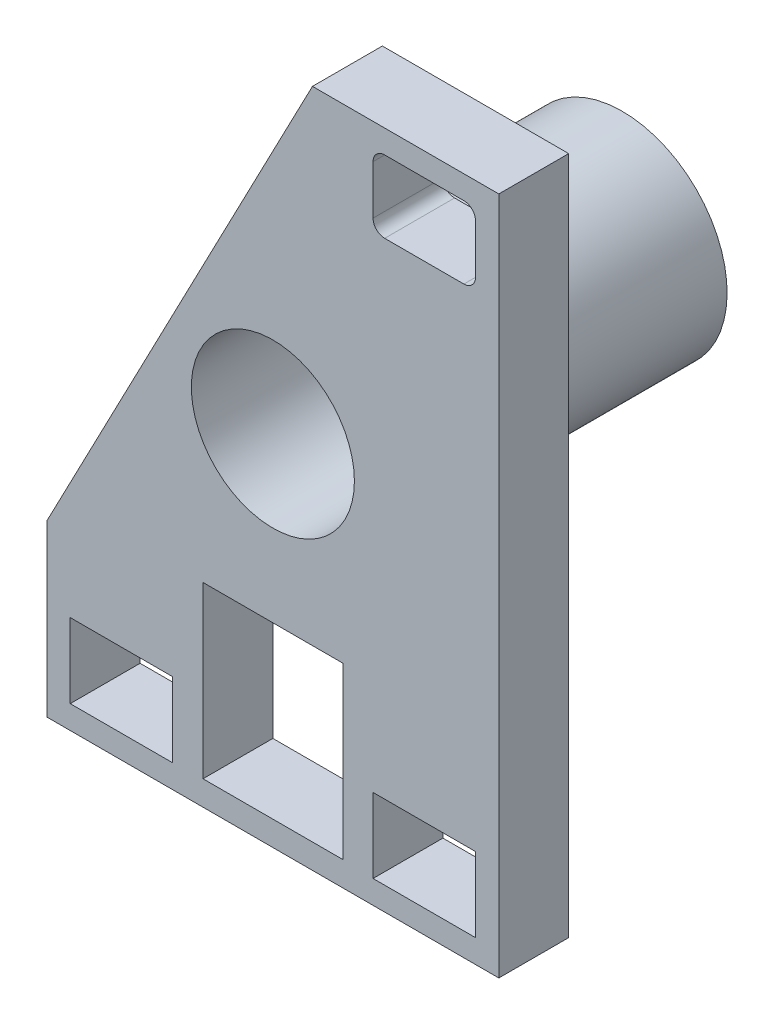
SolidWorks part; units mm, degrees
ref_plane "Front Plane" through (0, 0, 0) normal (0, 0, 1) x (1, 0, 0)
ref_plane "Top Plane" through (0, 0, 0) normal (0, 1, 0) x (1, 0, 0)
ref_plane "Right Plane" through (0, 0, 0) normal (1, 0, 0) x (0, 0, -1)
sketch "Sketch2" plane through (0, 0, 0) normal (0, 0, 1) x (1, 0, 0)
  line L0 (5.1046, -104.9632) -> (70.1046, -104.9632) construction
  line L1 (5.1046, 135.0368) -> (5.1046, -104.9632) construction
  line L2 (70.1046, -104.9632) -> (70.1046, 135.0368) construction
  line L3 (70.1046, 135.0368) -> (26.1046, 135.0368) construction
  line L4 (26.1046, 135.0368) -> (-59.8954, -32.9944) construction
  line L5 (-59.8954, -32.9944) -> (-59.8954, -104.9632) construction
  line L6 (-59.8954, -104.9632) -> (5.1046, -104.9632) construction
  line L7 (92.1046, 148.2211) -> (92.1046, -130.9632) construction
  line L8 (48.1046, 154.3078) -> (48.1046, -150.1586) construction
  line L9 (48.1046, 135.0368) -> (92.1046, 135.0368) construction
  line L10 (22.1046, 160.5368) -> (102.1046, 160.5368)
  line L11 (48.1046, 150.5368) -> (92.1046, 150.5368)
  line L12 (48.1046, 150.5368) -> (48.1046, 119.5368)
  line L13 (48.1046, 119.5368) -> (92.1046, 119.5368)
  line L14 (92.1046, 150.5368) -> (92.1046, 119.5368)
  line L15 (48.1046, 150.5368) -> (92.1046, 119.5368) construction
  line L16 (48.1046, 119.5368) -> (92.1046, 150.5368) construction
  line L17 (48.1046, -88.9632) -> (92.1046, -88.9632)
  line L18 (48.1046, -88.9632) -> (48.1046, -120.9632)
  line L19 (48.1046, -120.9632) -> (92.1046, -120.9632)
  line L20 (92.1046, -88.9632) -> (92.1046, -120.9632)
  line L21 (48.1046, -88.9632) -> (92.1046, -120.9632) construction
  line L22 (48.1046, -120.9632) -> (92.1046, -88.9632) construction
  line L23 (-81.8954, -88.9632) -> (-37.8954, -88.9632)
  line L24 (-81.8954, -88.9632) -> (-81.8954, -120.9632)
  line L25 (-81.8954, -120.9632) -> (-37.8954, -120.9632)
  line L26 (-37.8954, -88.9632) -> (-37.8954, -120.9632)
  line L27 (-81.8954, -88.9632) -> (-37.8954, -120.9632) construction
  line L28 (-81.8954, -120.9632) -> (-37.8954, -88.9632) construction
  line L29 (102.1046, 160.5368) -> (102.1046, -130.9632)
  line L30 (102.1046, -130.9632) -> (-91.8954, -130.9632)
  line L31 (-91.8954, -130.9632) -> (-91.8954, -57.9632)
  line L32 (22.1046, 160.5368) -> (-91.8954, -57.9632)
  line L34 (-24.8954, -47.396) -> (35.1046, -47.396)
  line L35 (-24.8954, -47.396) -> (-24.8954, -120.396)
  line L36 (-24.8954, -120.396) -> (35.1046, -120.396)
  line L37 (35.1046, -47.396) -> (35.1046, -120.396)
  line L38 (-24.8954, -47.396) -> (35.1046, -120.396) construction
  line L39 (-24.8954, -120.396) -> (35.1046, -47.396) construction
  circle A0 centre (5.1046, 15.0368) radius 45 construction
  point P13 (70.1046, 135.0368)
  point P30 (5.1046, -83.896)
  dimension "D7" = 90
  dimension "D8" = 10
  dimension "D1" = 240
  dimension "D2" = 130
  dimension "D3" = 44
  dimension "D4" = 31
  dimension "D5" = 32
  dimension "D6" = 44
  dimension "D9" = 10
  dimension "D10" = 10
  dimension "D11" = 10
  dimension "D12" = 73
  dimension "D13" = 60
  dimension "D14" = 80
  dimension "D15" = 73
extrude "Boss-Extrude1" add sketch "Sketch2" along normal blind 30
sketch "Sketch3" plane through (0, 0, 0) normal (0, 0, -1) x (-1, 0, 0)
  line L0 (-92.1046, 150.5368) -> (-48.1046, 150.5368) construction
  line L1 (81.8954, -88.9632) -> (81.8954, -120.9632) construction
  line L2 (-92.1046, -120.9632) -> (-92.1046, -88.9632) construction
  line L3 (-92.1046, 150.5368) -> (-48.1046, 150.5368)
  line L4 (81.8954, -88.9632) -> (81.8954, -120.9632)
  line L5 (-92.1046, -120.9632) -> (-92.1046, -88.9632)
  line L6 (-92.1046, -104.9632) -> (81.8954, -104.9632) construction
  line L7 (81.8954, -104.9632) -> (-48.1046, 150.5368) construction
  line L8 (-5.1046, 150.5368) -> (-5.1046, -104.9632) construction
  circle A0 centre (-5.1046, 22.7868) radius 45
  circle A1 centre (-5.1046, 22.7868) radius 35
  dimension "D1" = 90
  dimension "D2" = 70
extrude "Boss-Extrude2" add sketch "Sketch3" along normal blind 120 contours A0 A1 region at (48.8318, 22.7868, 0)
fillet "Fillet1" radius 5 4 edges at (92.1046, 119.5368, 15) (48.1046, 119.5368, 15) (92.1046, 150.5368, 15) (48.1046, 150.5368, 15)
fillet "Fillet2" radius 10 1 edges at (-39.8954, 22.7868, 0)
sketch "Sketch4" plane through (0, 0, 30) normal (0, 0, 1) x (1, 0, 0)
  line L5 (22.1046, 160.5368) -> (-91.8954, -57.9632)
  line L6 (-91.8954, -57.9632) -> (-91.8954, -130.9632)
  line L7 (-91.8954, -130.9632) -> (102.1046, -130.9632)
  line L8 (102.1046, -130.9632) -> (102.1046, 160.5368)
  line L9 (102.1046, 160.5368) -> (22.1046, 160.5368)
  line L10 (22.1046, 160.5368) -> (-91.8954, -57.9632)
  line L11 (-91.8954, -57.9632) -> (-91.8954, -130.9632)
  line L12 (-91.8954, -130.9632) -> (102.1046, -130.9632)
  line L14 (102.1046, 160.5368) -> (22.1046, 160.5368)
  circle A0 centre (5.1046, 22.7868) radius 35 construction
  circle A1 centre (5.1046, 22.7868) radius 35
  dimension "D1" = 0
extrude "Cut-Extrude2" cut sketch "Sketch4" against normal blind 120 contours A1 region at (5.1046, 22.7868, 30)
